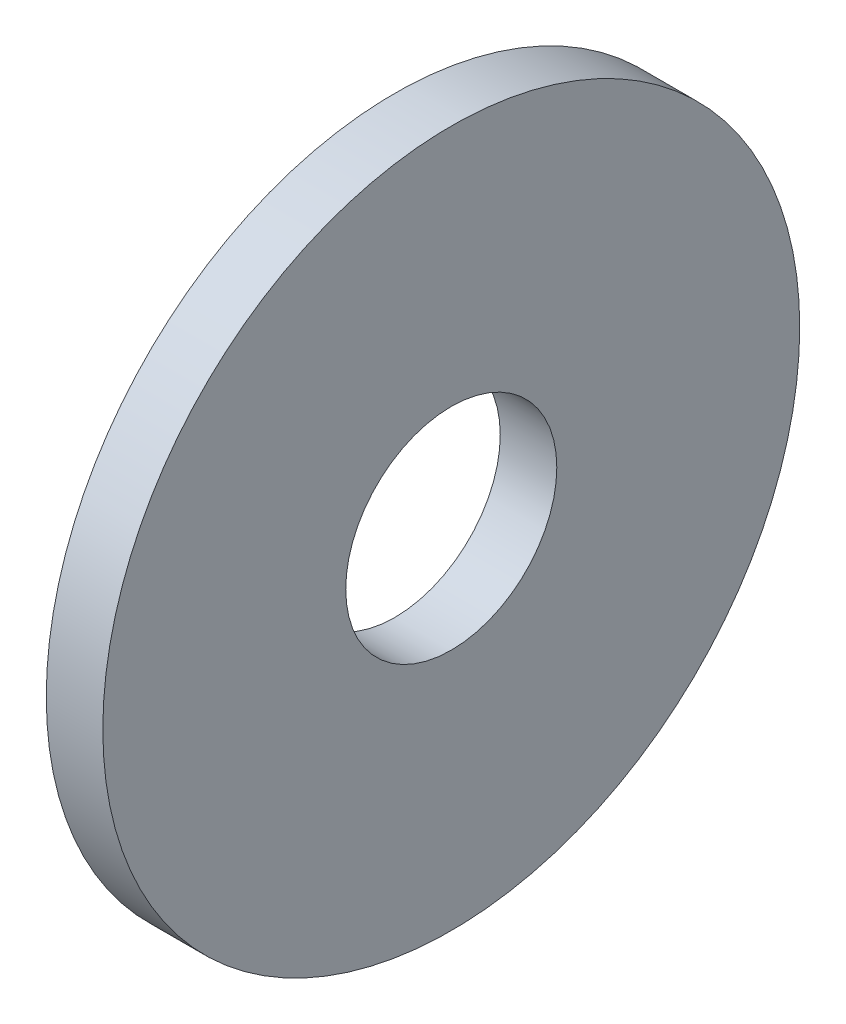
SolidWorks part; units mm, degrees
material "Stainless Steel (ferritic)"
ref_plane "Front Plane" through (0, 0, 0) normal (0, 0, 1) x (1, 0, 0)
ref_plane "Top Plane" through (0, 0, 0) normal (0, 1, 0) x (1, 0, 0)
ref_plane "Right Plane" through (0, 0, 0) normal (1, 0, 0) x (0, 0, -1)
sketch "Sketch1" plane through (0, 0, 0) normal (1, 0, 0) x (0, 0, -1)
  circle A0 centre (0, 0) radius 11.1125
  circle A1 centre (0, 0) radius 3.3655
  dimension "OD" = 22.225
  dimension "ID" = 6.731
extrude "Boss-Extrude1" add sketch "Sketch1" along normal blind 1.8034
ref_axis "Center Axis 1" through (1.8936, 0, 0) along (-1, 0, 0)
ref_plane "Contact Plane 1" through (0, 0, 0) normal (-1, 0, 0) x (0, 0, 1)
